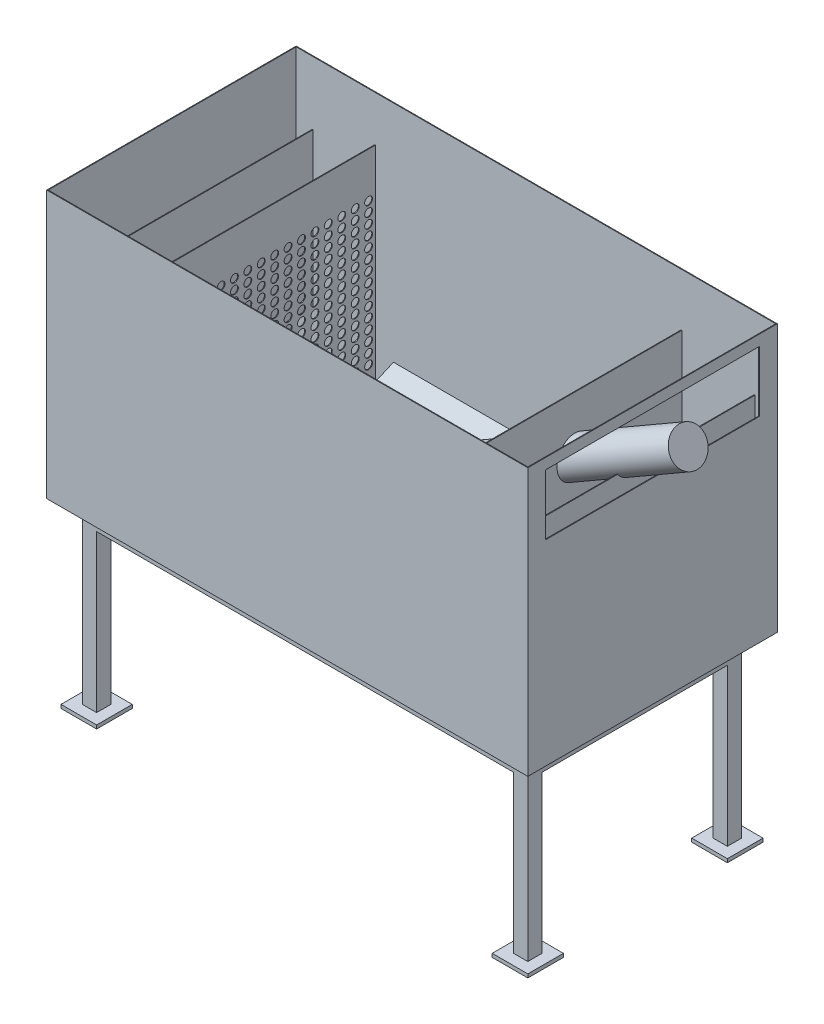
SolidWorks part; units mm, degrees
ref_plane "Спереди" through (0, 0, 0) normal (0, 0, 1) x (1, 0, 0)
ref_plane "Сверху" through (0, 0, 0) normal (0, 1, 0) x (1, 0, 0)
ref_plane "Справа" through (0, 0, 0) normal (1, 0, 0) x (0, 0, -1)
sketch "MASTER_FOOTPRINT" plane through (0, 0, 0) normal (0, 1, 0) x (1, 0, 0)
  line L1 (0, 0) -> (1350, 0)
  line L2 (0, 0) -> (0, 700)
  line L3 (0, 700) -> (1350, 700)
  line L4 (1350, 0) -> (1350, 700)
  dimension "D1" = 1350
  dimension "D2" = 700
extrude "BATH_BASE_PLATE" add sketch "MASTER_FOOTPRINT" along normal blind 750
shell "BATH_SHELL_2MM" thickness 2 removed face at (675, 750, -350)
sketch "Эскиз1" plane through (0, 0, 0) normal (1, 0, 0) x (0, 0, -1)
  circle A0 centre (350, 420) radius 50
extrude "INLET_D100_OPENING" cut sketch "Эскиз1" along normal blind 10
sketch "Эскиз2" plane through (0, 0, 0) normal (1, 0, 0) x (0, 0, -1)
  line L1 (80, 220) -> (620, 220)
  line L2 (80, 220) -> (80, 650)
  line L3 (80, 650) -> (620, 650)
  line L4 (620, 220) -> (620, 650)
extrude "INLET_IMPACT_BAFFLE" add sketch "Эскиз2" along normal blind 2 from offset 125 separate body
sketch "Эскиз3" plane through (0, 0, 0) normal (1, 0, 0) x (0, 0, -1)
  line L1 (30, 2) -> (670, 2)
  line L2 (30, 2) -> (30, 650)
  line L3 (30, 650) -> (670, 650)
  line L4 (670, 2) -> (670, 650)
  circle A0 centre (48.8235, 125) radius 11
  circle A1 centre (48.8235, 153.5) radius 11
  circle A2 centre (48.8235, 182) radius 11
  circle A3 centre (48.8235, 210.5) radius 11
  circle A4 centre (48.8235, 239) radius 11
  circle A5 centre (48.8235, 267.5) radius 11
  circle A6 centre (48.8235, 296) radius 11
  circle A7 centre (48.8235, 324.5) radius 11
  circle A8 centre (48.8235, 353) radius 11
  circle A9 centre (48.8235, 381.5) radius 11
  circle A10 centre (48.8235, 410) radius 11
  circle A11 centre (48.8235, 438.5) radius 11
  circle A12 centre (48.8235, 467) radius 11
  circle A13 centre (48.8235, 495.5) radius 11
  circle A14 centre (48.8235, 524) radius 11
  circle A15 centre (86.4706, 125) radius 11
  circle A16 centre (86.4706, 153.5) radius 11
  circle A17 centre (86.4706, 182) radius 11
  circle A18 centre (86.4706, 210.5) radius 11
  circle A19 centre (86.4706, 239) radius 11
  circle A20 centre (86.4706, 267.5) radius 11
  circle A21 centre (86.4706, 296) radius 11
  circle A22 centre (86.4706, 324.5) radius 11
  circle A23 centre (86.4706, 353) radius 11
  circle A24 centre (86.4706, 381.5) radius 11
  circle A25 centre (86.4706, 410) radius 11
  circle A26 centre (86.4706, 438.5) radius 11
  circle A27 centre (86.4706, 467) radius 11
  circle A28 centre (86.4706, 495.5) radius 11
  circle A29 centre (86.4706, 524) radius 11
  circle A30 centre (124.1176, 125) radius 11
  circle A31 centre (124.1176, 153.5) radius 11
  circle A32 centre (124.1176, 182) radius 11
  circle A33 centre (124.1176, 210.5) radius 11
  circle A34 centre (124.1176, 239) radius 11
  circle A35 centre (124.1176, 267.5) radius 11
  circle A36 centre (124.1176, 296) radius 11
  circle A37 centre (124.1176, 324.5) radius 11
  circle A38 centre (124.1176, 353) radius 11
  circle A39 centre (124.1176, 381.5) radius 11
  circle A40 centre (124.1176, 410) radius 11
  circle A41 centre (124.1176, 438.5) radius 11
  circle A42 centre (124.1176, 467) radius 11
  circle A43 centre (124.1176, 495.5) radius 11
  circle A44 centre (124.1176, 524) radius 11
  circle A45 centre (161.7647, 125) radius 11
  circle A46 centre (161.7647, 153.5) radius 11
  circle A47 centre (161.7647, 182) radius 11
  circle A48 centre (161.7647, 210.5) radius 11
  circle A49 centre (161.7647, 239) radius 11
  circle A50 centre (161.7647, 267.5) radius 11
  circle A51 centre (161.7647, 296) radius 11
  circle A52 centre (161.7647, 324.5) radius 11
  circle A53 centre (161.7647, 353) radius 11
  circle A54 centre (161.7647, 381.5) radius 11
  circle A55 centre (161.7647, 410) radius 11
  circle A56 centre (161.7647, 438.5) radius 11
  circle A57 centre (161.7647, 467) radius 11
  circle A58 centre (161.7647, 495.5) radius 11
  circle A59 centre (161.7647, 524) radius 11
  circle A60 centre (199.4118, 125) radius 11
  circle A61 centre (199.4118, 153.5) radius 11
  circle A62 centre (199.4118, 182) radius 11
  circle A63 centre (199.4118, 210.5) radius 11
  circle A64 centre (199.4118, 239) radius 11
  circle A65 centre (199.4118, 267.5) radius 11
  circle A66 centre (199.4118, 296) radius 11
  circle A67 centre (199.4118, 324.5) radius 11
  circle A68 centre (199.4118, 353) radius 11
  circle A69 centre (199.4118, 381.5) radius 11
  circle A70 centre (199.4118, 410) radius 11
  circle A71 centre (199.4118, 438.5) radius 11
  circle A72 centre (199.4118, 467) radius 11
  circle A73 centre (199.4118, 495.5) radius 11
  circle A74 centre (199.4118, 524) radius 11
  circle A75 centre (237.0588, 125) radius 11
  circle A76 centre (237.0588, 153.5) radius 11
  circle A77 centre (237.0588, 182) radius 11
  circle A78 centre (237.0588, 210.5) radius 11
  circle A79 centre (237.0588, 239) radius 11
  circle A80 centre (237.0588, 267.5) radius 11
  circle A81 centre (237.0588, 296) radius 11
  circle A82 centre (237.0588, 324.5) radius 11
  circle A83 centre (237.0588, 353) radius 11
  circle A84 centre (237.0588, 381.5) radius 11
  circle A85 centre (237.0588, 410) radius 11
  circle A86 centre (237.0588, 438.5) radius 11
  circle A87 centre (237.0588, 467) radius 11
  circle A88 centre (237.0588, 495.5) radius 11
  circle A89 centre (237.0588, 524) radius 11
  circle A90 centre (274.7059, 125) radius 11
  circle A91 centre (274.7059, 153.5) radius 11
  circle A92 centre (274.7059, 182) radius 11
  circle A93 centre (274.7059, 210.5) radius 11
  circle A94 centre (274.7059, 239) radius 11
  circle A95 centre (274.7059, 267.5) radius 11
  circle A96 centre (274.7059, 296) radius 11
  circle A97 centre (274.7059, 324.5) radius 11
  circle A98 centre (274.7059, 353) radius 11
  circle A99 centre (274.7059, 381.5) radius 11
  circle A100 centre (274.7059, 410) radius 11
  circle A101 centre (274.7059, 438.5) radius 11
  circle A102 centre (274.7059, 467) radius 11
  circle A103 centre (274.7059, 495.5) radius 11
  circle A104 centre (274.7059, 524) radius 11
  circle A105 centre (312.3529, 125) radius 11
  circle A106 centre (312.3529, 153.5) radius 11
  circle A107 centre (312.3529, 182) radius 11
  circle A108 centre (312.3529, 210.5) radius 11
  circle A109 centre (312.3529, 239) radius 11
  circle A110 centre (312.3529, 267.5) radius 11
  circle A111 centre (312.3529, 296) radius 11
  circle A112 centre (312.3529, 324.5) radius 11
  circle A113 centre (312.3529, 353) radius 11
  circle A114 centre (312.3529, 381.5) radius 11
  circle A115 centre (312.3529, 410) radius 11
  circle A116 centre (312.3529, 438.5) radius 11
  circle A117 centre (312.3529, 467) radius 11
  circle A118 centre (312.3529, 495.5) radius 11
  circle A119 centre (312.3529, 524) radius 11
  circle A120 centre (350, 125) radius 11
  circle A121 centre (350, 153.5) radius 11
  circle A122 centre (350, 182) radius 11
  circle A123 centre (350, 210.5) radius 11
  circle A124 centre (350, 239) radius 11
  circle A125 centre (350, 267.5) radius 11
  circle A126 centre (350, 296) radius 11
  circle A127 centre (350, 324.5) radius 11
  circle A128 centre (350, 353) radius 11
  circle A129 centre (350, 381.5) radius 11
  circle A130 centre (350, 410) radius 11
  circle A131 centre (350, 438.5) radius 11
  circle A132 centre (350, 467) radius 11
  circle A133 centre (350, 495.5) radius 11
  circle A134 centre (350, 524) radius 11
  circle A135 centre (387.6471, 125) radius 11
  circle A136 centre (387.6471, 153.5) radius 11
  circle A137 centre (387.6471, 182) radius 11
  circle A138 centre (387.6471, 210.5) radius 11
  circle A139 centre (387.6471, 239) radius 11
  circle A140 centre (387.6471, 267.5) radius 11
  circle A141 centre (387.6471, 296) radius 11
  circle A142 centre (387.6471, 324.5) radius 11
  circle A143 centre (387.6471, 353) radius 11
  circle A144 centre (387.6471, 381.5) radius 11
  circle A145 centre (387.6471, 410) radius 11
  circle A146 centre (387.6471, 438.5) radius 11
  circle A147 centre (387.6471, 467) radius 11
  circle A148 centre (387.6471, 495.5) radius 11
  circle A149 centre (387.6471, 524) radius 11
  circle A150 centre (425.2941, 125) radius 11
  circle A151 centre (425.2941, 153.5) radius 11
  circle A152 centre (425.2941, 182) radius 11
  circle A153 centre (425.2941, 210.5) radius 11
  circle A154 centre (425.2941, 239) radius 11
  circle A155 centre (425.2941, 267.5) radius 11
  circle A156 centre (425.2941, 296) radius 11
  circle A157 centre (425.2941, 324.5) radius 11
  circle A158 centre (425.2941, 353) radius 11
  circle A159 centre (425.2941, 381.5) radius 11
  circle A160 centre (425.2941, 410) radius 11
  circle A161 centre (425.2941, 438.5) radius 11
  circle A162 centre (425.2941, 467) radius 11
  circle A163 centre (425.2941, 495.5) radius 11
  circle A164 centre (425.2941, 524) radius 11
  circle A165 centre (462.9412, 125) radius 11
  circle A166 centre (462.9412, 153.5) radius 11
  circle A167 centre (462.9412, 182) radius 11
  circle A168 centre (462.9412, 210.5) radius 11
  circle A169 centre (462.9412, 239) radius 11
  circle A170 centre (462.9412, 267.5) radius 11
  circle A171 centre (462.9412, 296) radius 11
  circle A172 centre (462.9412, 324.5) radius 11
  circle A173 centre (462.9412, 353) radius 11
  circle A174 centre (462.9412, 381.5) radius 11
  circle A175 centre (462.9412, 410) radius 11
  circle A176 centre (462.9412, 438.5) radius 11
  circle A177 centre (462.9412, 467) radius 11
  circle A178 centre (462.9412, 495.5) radius 11
  circle A179 centre (462.9412, 524) radius 11
  circle A180 centre (500.5882, 125) radius 11
  circle A181 centre (500.5882, 153.5) radius 11
  circle A182 centre (500.5882, 182) radius 11
  circle A183 centre (500.5882, 210.5) radius 11
  circle A184 centre (500.5882, 239) radius 11
  circle A185 centre (500.5882, 267.5) radius 11
  circle A186 centre (500.5882, 296) radius 11
  circle A187 centre (500.5882, 324.5) radius 11
  circle A188 centre (500.5882, 353) radius 11
  circle A189 centre (500.5882, 381.5) radius 11
  circle A190 centre (500.5882, 410) radius 11
  circle A191 centre (500.5882, 438.5) radius 11
  circle A192 centre (500.5882, 467) radius 11
  circle A193 centre (500.5882, 495.5) radius 11
  circle A194 centre (500.5882, 524) radius 11
  circle A195 centre (538.2353, 125) radius 11
  circle A196 centre (538.2353, 153.5) radius 11
  circle A197 centre (538.2353, 182) radius 11
  circle A198 centre (538.2353, 210.5) radius 11
  circle A199 centre (538.2353, 239) radius 11
  circle A200 centre (538.2353, 267.5) radius 11
  circle A201 centre (538.2353, 296) radius 11
  circle A202 centre (538.2353, 324.5) radius 11
  circle A203 centre (538.2353, 353) radius 11
  circle A204 centre (538.2353, 381.5) radius 11
  circle A205 centre (538.2353, 410) radius 11
  circle A206 centre (538.2353, 438.5) radius 11
  circle A207 centre (538.2353, 467) radius 11
  circle A208 centre (538.2353, 495.5) radius 11
  circle A209 centre (538.2353, 524) radius 11
  circle A210 centre (575.8824, 125) radius 11
  circle A211 centre (575.8824, 153.5) radius 11
  circle A212 centre (575.8824, 182) radius 11
  circle A213 centre (575.8824, 210.5) radius 11
  circle A214 centre (575.8824, 239) radius 11
  circle A215 centre (575.8824, 267.5) radius 11
  circle A216 centre (575.8824, 296) radius 11
  circle A217 centre (575.8824, 324.5) radius 11
  circle A218 centre (575.8824, 353) radius 11
  circle A219 centre (575.8824, 381.5) radius 11
  circle A220 centre (575.8824, 410) radius 11
  circle A221 centre (575.8824, 438.5) radius 11
  circle A222 centre (575.8824, 467) radius 11
  circle A223 centre (575.8824, 495.5) radius 11
  circle A224 centre (575.8824, 524) radius 11
  circle A225 centre (613.5294, 125) radius 11
  circle A226 centre (613.5294, 153.5) radius 11
  circle A227 centre (613.5294, 182) radius 11
  circle A228 centre (613.5294, 210.5) radius 11
  circle A229 centre (613.5294, 239) radius 11
  circle A230 centre (613.5294, 267.5) radius 11
  circle A231 centre (613.5294, 296) radius 11
  circle A232 centre (613.5294, 324.5) radius 11
  circle A233 centre (613.5294, 353) radius 11
  circle A234 centre (613.5294, 381.5) radius 11
  circle A235 centre (613.5294, 410) radius 11
  circle A236 centre (613.5294, 438.5) radius 11
  circle A237 centre (613.5294, 467) radius 11
  circle A238 centre (613.5294, 495.5) radius 11
  circle A239 centre (613.5294, 524) radius 11
  circle A240 centre (651.1765, 125) radius 11
  circle A241 centre (651.1765, 153.5) radius 11
  circle A242 centre (651.1765, 182) radius 11
  circle A243 centre (651.1765, 210.5) radius 11
  circle A244 centre (651.1765, 239) radius 11
  circle A245 centre (651.1765, 267.5) radius 11
  circle A246 centre (651.1765, 296) radius 11
  circle A247 centre (651.1765, 324.5) radius 11
  circle A248 centre (651.1765, 353) radius 11
  circle A249 centre (651.1765, 381.5) radius 11
  circle A250 centre (651.1765, 410) radius 11
  circle A251 centre (651.1765, 438.5) radius 11
  circle A252 centre (651.1765, 467) radius 11
  circle A253 centre (651.1765, 495.5) radius 11
  circle A254 centre (651.1765, 524) radius 11
extrude "DISTRIBUTOR_D22" add sketch "Эскиз3" along normal blind 2 from offset 250 separate body
sketch "Эскиз4" plane through (0, 0, 0) normal (1, 0, 0) x (0, 0, -1)
  line L1 (50, 320) -> (650, 320)
  line L2 (50, 320) -> (50, 650)
  line L3 (50, 650) -> (650, 650)
  line L4 (650, 320) -> (650, 650)
extrude "OUTLET_SUBMERGED_BAFFLE" add sketch "Эскиз4" along normal blind 2 from offset 1130 separate body
sketch "Эскиз5" plane through (0, 0, 0) normal (1, 0, 0) x (0, 0, -1)
  line L1 (5, 2) -> (695, 2)
  line L2 (5, 2) -> (5, 550)
  line L3 (5, 550) -> (695, 550)
  line L4 (695, 2) -> (695, 550)
extrude "OVERFLOW_WEIR_Z550" add sketch "Эскиз5" along normal blind 2 from offset 1290 separate body
sketch "Эскиз6" plane through (0, 0, 0) normal (1, 0, 0) x (0, 0, -1)
  line L1 (50, 550) -> (650, 550)
  line L2 (50, 550) -> (50, 720)
  line L3 (50, 720) -> (650, 720)
  line L4 (650, 550) -> (650, 720)
extrude "OUTLET_WEIR_SLOT_W600" cut sketch "Эскиз6" along normal blind 10 from offset 1345
sketch "Эскиз7" plane through (0, 0, 0) normal (1, 0, 0) x (0, 0, -1)
  line L0 (2, -1) -> (2, 120)
  line L1 (2, 120) -> (280, -1)
  line L2 (280, -1) -> (2, -1)
  line L3 (698, -1) -> (698, 120)
  line L4 (698, 120) -> (420, -1)
  line L5 (420, -1) -> (698, -1)
extrude "SLOPED_SEDIMENT_FLOOR" add sketch "Эскиз7" along normal blind 825 from offset 275
sketch3d "SCREW_AXIS_30DEG_REFERENCE"
  line L0 (400, 70, -350) -> (1450, 676.2178, -350)
sketch "Эскиз8" plane through (0, 0, 0) normal (0, 1, 0) x (1, 0, 0)
  line L1 (50, 50) -> (90, 50)
  line L2 (50, 50) -> (50, 90)
  line L3 (50, 90) -> (90, 90)
  line L4 (90, 50) -> (90, 90)
  line L6 (50, 610) -> (90, 610)
  line L7 (50, 610) -> (50, 650)
  line L8 (50, 650) -> (90, 650)
  line L9 (90, 610) -> (90, 650)
  line L11 (1260, 50) -> (1300, 50)
  line L12 (1260, 50) -> (1260, 90)
  line L13 (1260, 90) -> (1300, 90)
  line L14 (1300, 50) -> (1300, 90)
  line L16 (1260, 610) -> (1300, 610)
  line L17 (1260, 610) -> (1260, 650)
  line L18 (1260, 650) -> (1300, 650)
  line L19 (1300, 610) -> (1300, 650)
extrude "FRAME_LEGS_40X40_H500" add sketch "Эскиз8" against normal blind 500
sketch "Эскиз9" plane through (0, 0, 0) normal (0, 1, 0) x (1, 0, 0)
  line L1 (50, 50) -> (1300, 50)
  line L2 (50, 50) -> (50, 90)
  line L3 (50, 90) -> (1300, 90)
  line L4 (1300, 50) -> (1300, 90)
  line L6 (50, 610) -> (1300, 610)
  line L7 (50, 610) -> (50, 650)
  line L8 (50, 650) -> (1300, 650)
  line L9 (1300, 610) -> (1300, 650)
extrude "FRAME_LONGITUDINAL_RAILS" add sketch "Эскиз9" against normal blind 40 from offset 20 offset against normal yes
sketch "Эскиз10" plane through (0, 0, 0) normal (0, 1, 0) x (1, 0, 0)
  line L1 (50, 90) -> (90, 90)
  line L2 (50, 90) -> (50, 610)
  line L3 (50, 610) -> (90, 610)
  line L4 (90, 90) -> (90, 610)
  line L6 (1260, 90) -> (1300, 90)
  line L7 (1260, 90) -> (1260, 610)
  line L8 (1260, 610) -> (1300, 610)
  line L9 (1300, 90) -> (1300, 610)
extrude "FRAME_TRANSVERSE_RAILS" add sketch "Эскиз10" against normal blind 40 from offset 20 offset against normal yes
sketch "Эскиз11" plane through (0, 0, 0) normal (0, 1, 0) x (1, 0, 0)
  line L1 (20, 20) -> (120, 20)
  line L2 (20, 20) -> (20, 120)
  line L3 (20, 120) -> (120, 120)
  line L4 (120, 20) -> (120, 120)
  line L6 (20, 580) -> (120, 580)
  line L7 (20, 580) -> (20, 680)
  line L8 (20, 680) -> (120, 680)
  line L9 (120, 580) -> (120, 680)
  line L11 (1230, 20) -> (1330, 20)
  line L12 (1230, 20) -> (1230, 120)
  line L13 (1230, 120) -> (1330, 120)
  line L14 (1330, 20) -> (1330, 120)
  line L16 (1230, 580) -> (1330, 580)
  line L17 (1230, 580) -> (1230, 680)
  line L18 (1230, 680) -> (1330, 680)
  line L19 (1330, 580) -> (1330, 680)
extrude "FRAME_FOOT_PADS_100X100" add sketch "Эскиз11" against normal blind 10 from offset 500 offset against normal yes
sweep "SCREW_OUTER_ENVELOPE_D100" add path "SCREW_AXIS_30DEG_REFERENCE" circular profile diameter 100 parameters "D3"=100
equation "\"AI_Q_Peak\"= 0.006"
equation "\"AI_B_Bath\"= 700"
equation "\"AI_L_Settle\"= 900"
equation "\"AI_L_Inlet\"= 250"
equation "\"AI_L_Outlet\"= 200"
equation "\"AI_L_Bath\"= 1350"
equation "\"AI_H_Water\"= 550"
equation "\"AI_H_Freeboard\"= 200"
equation "\"AI_H_Bath\"= 750"
equation "\"AI_Shell_Thickness\"= 2"
equation "\"AI_Inlet_DN\"= 100"
equation "\"AI_Weir_Width\"= 600"
equation "\"AI_Inlet_Baffle_Offset\"= 125"
equation "\"AI_Distributor_Open_Area\"= 0.28"
equation "\"AI_Distributor_Hole_Dia\"= 22"
equation "\"AI_Distributor_Blind_Zone\"= 110"
equation "\"AI_Outlet_Baffle_Depth\"= 250"
equation "\"AI_Screw_Diameter\"= 100"
equation "\"AI_Screw_Pitch\"= 100"
equation "\"AI_Screw_Angle\"= 30"
equation "\"AI_Screw_Rpm\"= 15"
equation "\"AI_Screw_Clearance\"= 5"
equation "\"AI_Liner_Thickness\"= 5"
equation "\"AI_Discharge_Height\"= 650"
equation "\"AI_Frame_Height\"= 500"
equation "\"D1@MASTER_FOOTPRINT\" = \"AI_L_Bath\""
equation "\"D2@MASTER_FOOTPRINT\" = \"AI_B_Bath\""
equation "\"D1@BATH_BASE_PLATE\" = \"AI_H_Bath\""
